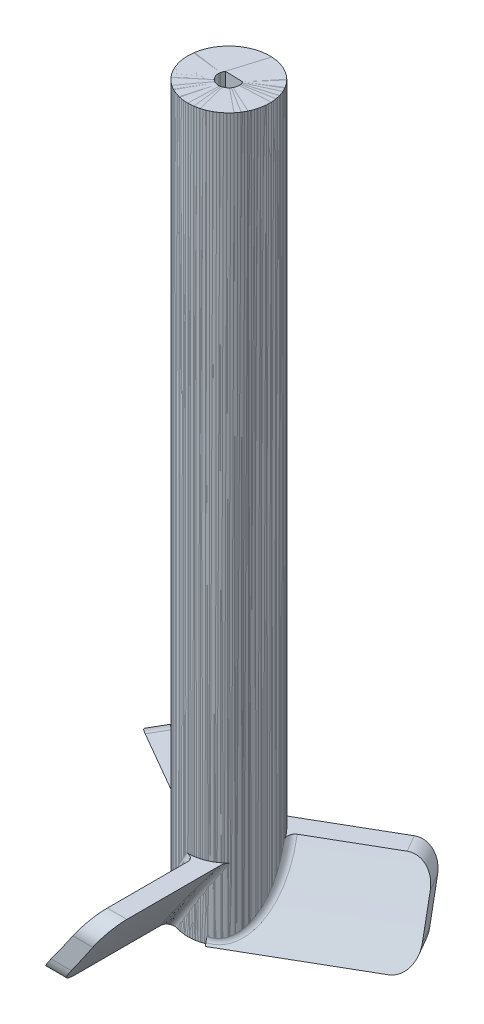
SolidWorks part; units mm, degrees
ref_plane "Front Plane" through (0, 0, 0) normal (0, 0, 1) x (1, 0, 0)
ref_plane "Top Plane" through (0, 0, 0) normal (0, 1, 0) x (1, 0, 0)
ref_plane "Right Plane" through (0, 0, 0) normal (1, 0, 0) x (0, 0, -1)
sketch "Sketch7" plane through (0, 0, 0) normal (0, 0, 1) x (1, 0, 0)
  line L0 (3.5176, 0) -> (-3.5176, 0) construction
  line L1 (6.849, 7) -> (4.9497, 7)
  line L2 (0, 0) -> (2, 0)
  arc A0 (0, 0) -> (4.9497, 7) centre (-91.3778, 69.8639) ccw
  arc A1 (6.849, 7) -> (2, 0) centre (-91.3778, 69.8639) cw
  dimension "D2" = 7
extrude "Boss-Extrude2" add sketch "Sketch7" along normal blind 15 contours A0 L1 A1 L2
fillet "Fillet1" radius 2 2 edges at (1, 0, 15) (5.8994, 7, 15)
sketch "Sketch10" plane through (0, 0, 0) normal (0, 1, 0) x (1, 0, 0)
  line L0 (0.3156, 0) -> (8.1957, 0) construction
  line L1 (4.9497, 0) -> (0, 0) construction
  line L2 (6.849, 0) -> (4.9497, 0) construction
  line L3 (2, 0) -> (6.849, 0) construction
  line L4 (4.2556, 0) -> (4.2556, -0.5251)
  line L5 (3.1481, -1000) -> (3.1481, 49000) construction
  circle A0 centre (4.2556, -0.5251) radius 3.9749
  point P5 (3.1481, 0)
  point P10 (-1.8519, 0)
  point P14 (0, 0)
  point P16 (0, 0)
  point P17 (3.1481, 0)
  point P18 (0, 0)
  point P19 (0, 0)
  point P20 (0, 0)
  dimension "D4" = 5
extrude "Boss-Extrude3" add sketch "Sketch10" along normal blind 70 contours A0 region at (0.3932, 0, 0.5251)
fillet "Fillet4" radius 0.7 2 edges at (0.8155, 1.0797, 2.5163) (3.7358, 2.3821, 4.4659)
pattern_circular "CirPattern1" count 3 over 360 about axis through (4.2556, 70, 0.5251) along (0, -1, 0) of bodies 103 102
sketch "Sketch11" plane through (0, 70, 0) normal (0, 1, 0) x (1, 0, 0)
  line L0 (3.4046, 0) -> (5.1359, -0.0507)
  arc A1 (3.4046, 0) -> (5.1359, -0.0507) centre (4.2556, -0.5251) ccw
  circle A2 centre (4.2556, -0.5251) radius 3.9749 construction
extrude "Cut-Extrude1" cut sketch "Sketch11" against normal blind 40 contours A1 L0
equation "\"insidebladediameter\"=0.01"
equation "\"height\"= 0.007"
equation "\"bladethickness\"=0.002"
equation "\"insidebladeradius\"= \"insidebladediameter\" / 2"
equation "\"D1@Sketch7\"=\"bladethickness\""
equation "\"D2@Sketch7\"=\"height\""
equation "\"bladewidth\"= \"height\" * cos ( \"bladeangle\" )"
equation "\"bladelength\"= 0.015"
equation "\"D1@Boss-Extrude2\"=\"bladelength\""
equation "\"bladetipradius\"= 0.002"
equation "\"D1@Fillet1\"=\"bladetipradius\""
equation "\"fusedistance\"= 0.0045"
equation "\"motorrodheight\"=0.07"
equation "\"D1@Boss-Extrude3\"=\"motorrodheight\""
equation "\"numberofblades\"= 3"
equation "\"D1@CirPattern1\"=\"numberofblades\""
equation "\"roddiameter\"= ( \"bladewidth\" + 0.003 )"
equation "\"roddepth\"= 0.005"
equation "\"bladeangle\"= 45deg"
equation "\"m\"=1"
equation "\"flatfacedist\"= 0.0005"
equation "\"motorshaftdiameter\"=0.002"
equation "\"D1@Sketch11\"=\"motorshaftdiameter\"/2"
equation "\"D3@Sketch7\"=\"bladewidth\""
equation "\"D2@Sketch10\"=\"roddiameter\"/2-\"fusedistance\""
equation "\"D1@Sketch10\"=\"roddiameter\""
equation "\"D2@Sketch11\"=\"flatfacedist\""
equation "\"bladefilletradius\"= 0.0007"
equation "\"D1@Fillet4\"=\"bladefilletradius\""
